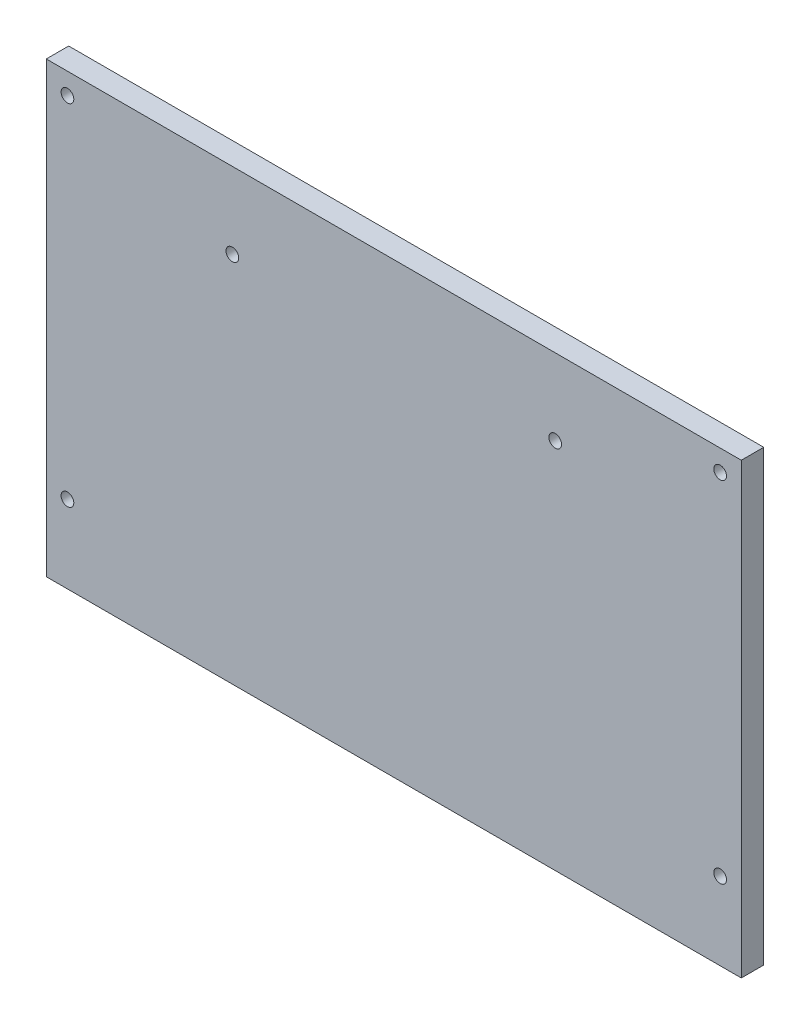
SolidWorks part; units mm, degrees
material "Acrylic (Medium-high impact)"
ref_plane "Front Plane" through (0, 0, 0) normal (0, 0, 1) x (1, 0, 0)
ref_plane "Top Plane" through (0, 0, 0) normal (0, 1, 0) x (1, 0, 0)
ref_plane "Right Plane" through (0, 0, 0) normal (1, 0, 0) x (0, 0, -1)
sketch "Sketch1" plane through (0, 0, 0) normal (0, 0, 1) x (1, 0, 0)
  line L1 (196.85, 127) -> (0, 127)
  line L2 (196.85, 127) -> (196.85, 0)
  line L3 (196.85, 0) -> (0, 0)
  line L4 (0, 127) -> (0, 0)
  line L5 (196.85, 127) -> (0, 0) construction
  line L6 (196.85, 0) -> (0, 127) construction
  point P0 (98.425, 63.5)
  dimension "D1" = 127
  dimension "D2" = 196.85
extrude "Boss-Extrude1" add sketch "Sketch1" along normal blind 6.35
hole_wizard "M3 Clearance Hole1" positions "Sketch2" profile "Sketch3" hole size "M3" standard "ANSI Metric" end condition through all
sketch "Sketch2" plane through (0, 0, 6.35) normal (0, 0, 1) x (1, 0, 0)
  line L0 (0, 127) -> (0, 0) construction
  line L1 (196.85, 127) -> (0, 127) construction
  line L2 (196.85, 0) -> (196.85, 127) construction
  line L3 (0, 0) -> (196.85, 0) construction
  point P0 (5.9944, 121.0056)
  point P2 (5.9944, 21.9964)
  point P4 (190.8556, 21.9964)
  point P6 (190.8556, 121.0056)
  dimension "D1" = 5.9944
  dimension "D2" = 5.9944
  dimension "D3" = 5.9944
  dimension "D4" = 21.9964
sketch "Sketch3" plane through (5.9944, 121.0056, 6.35) normal (1, 0, 0) x (0, -1, 0)
  line L0 (0, 0) -> (0, 6.35)
  line L1 (0, 6.35) -> (1.8, 6.35)
  line L2 (1.8, 6.35) -> (1.8, 0)
  line L5 (1.8, 0) -> (0, 0)
  line L11 (0, -6.35) -> (0, 107.95) construction
  dimension "Thru Hole Dia." = 3.6
  dimension "Thru Hole Depth" = 6.35
sketch "Sketch4" plane through (0, 0, 6.35) normal (0, 0, 1) x (1, 0, 0)
  line L0 (0, 127) -> (0, 0) construction
  line L1 (46.99, 107.95) -> (50.4952, 107.95)
  line L2 (46.99, 107.95) -> (46.99, 44.45)
  line L3 (46.99, 44.45) -> (50.4952, 44.45)
  line L4 (50.4952, 107.95) -> (50.4952, 44.45)
  line L5 (146.3548, 107.95) -> (149.86, 107.95)
  line L6 (146.3548, 107.95) -> (146.3548, 44.45)
  line L7 (146.3548, 44.45) -> (149.86, 44.45)
  line L8 (149.86, 107.95) -> (149.86, 44.45)
  line L9 (196.85, 0) -> (196.85, 127) construction
  line L10 (196.85, 127) -> (0, 127) construction
  dimension "D1" = 3.5052
  dimension "D2" = 63.5
  dimension "D3" = 46.99
  dimension "D4" = 46.99
  dimension "D5" = 19.05
extrude "Cut-Extrude1" [suppressed] cut sketch "Sketch4" against normal through all
sketch "Sketch5" plane through (0, 0, 6.35) normal (0, 0, 1) x (1, 0, 0)
  line L0 (0, 10.7092) -> (76.2, 0)
  line L1 (0, 127) -> (0, 0) construction
  line L2 (0, 0) -> (196.85, 0) construction
  line L3 (76.2, 0) -> (0, 0)
  line L4 (0, 0) -> (0, 10.7092)
  line L5 (120.65, 0) -> (196.85, 0)
  line L6 (196.85, 0) -> (196.85, 10.7092)
  line L7 (196.85, 0) -> (196.85, 127) construction
  line L8 (196.85, 10.7092) -> (120.65, 0)
  dimension "D1" = 8
  dimension "D2" = 8
  dimension "D3" = 76.2
  dimension "D4" = 76.2
extrude "Cut-Extrude2" [suppressed] cut sketch "Sketch5" against normal through all
hole_wizard "M3 Clearance Hole2" positions "Sketch6" profile "Sketch7" hole size "M3" standard "ANSI Metric" end condition through all
sketch "Sketch6" plane through (0, 0, 6.35) normal (0, 0, 1) x (1, 0, 0)
  line L0 (0, 127) -> (0, 0) construction
  line L1 (196.85, 127) -> (0, 127) construction
  point P0 (52.705, 105.41)
  point P2 (144.145, 105.41)
  dimension "D1" = 91.44
  dimension "D2" = 52.705
  dimension "D3" = 21.59
sketch "Sketch7" plane through (52.705, 105.41, 6.35) normal (1, 0, 0) x (0, -1, 0)
  line L0 (0, 0) -> (0, 6.35)
  line L1 (0, 6.35) -> (1.8, 6.35)
  line L2 (1.8, 6.35) -> (1.8, 0)
  line L5 (1.8, 0) -> (0, 0)
  line L11 (0, -6.35) -> (0, 107.95) construction
  dimension "Thru Hole Dia." = 3.6
  dimension "Thru Hole Depth" = 6.35
